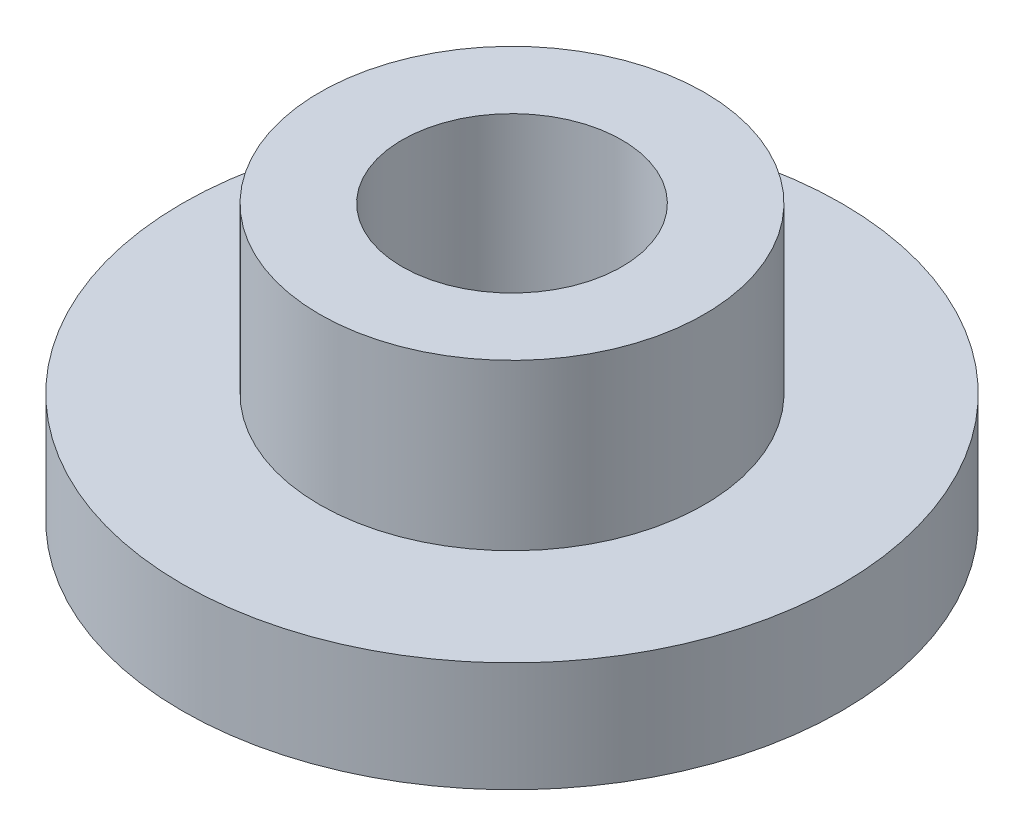
SolidWorks part; units mm, degrees
ref_plane "前视基准面" through (0, 0, 0) normal (0, 0, 1) x (1, 0, 0)
ref_plane "上视基准面" through (0, 0, 0) normal (0, 1, 0) x (1, 0, 0)
ref_plane "右视基准面" through (0, 0, 0) normal (1, 0, 0) x (0, 0, -1)
sketch "草图1" plane through (0, 0, 0) normal (0, 1, 0) x (1, 0, 0)
  circle A0 centre (0, 0) radius 3.5
  circle A1 centre (0, 0) radius 2
  circle A2 centre (0, 0) radius 6
  dimension "D1" = 4
  dimension "D2" = 7
  dimension "D3" = 12
extrude "凸台-拉伸1" add sketch "草图1" along normal blind 3 contours A0 A1 region at (-3.401, 0, 0)
extrude "凸台-拉伸2" add sketch "草图1<3>" against normal blind 2 contours A2 A0 | A0 A1 region at (-3.401, 0, 0) region at (-5.8303, 0, 0)
sketch "草图1<3>" plane through (0, 0, 0) normal (0, 1, 0) x (1, 0, 0) same geometry as "草图1"
